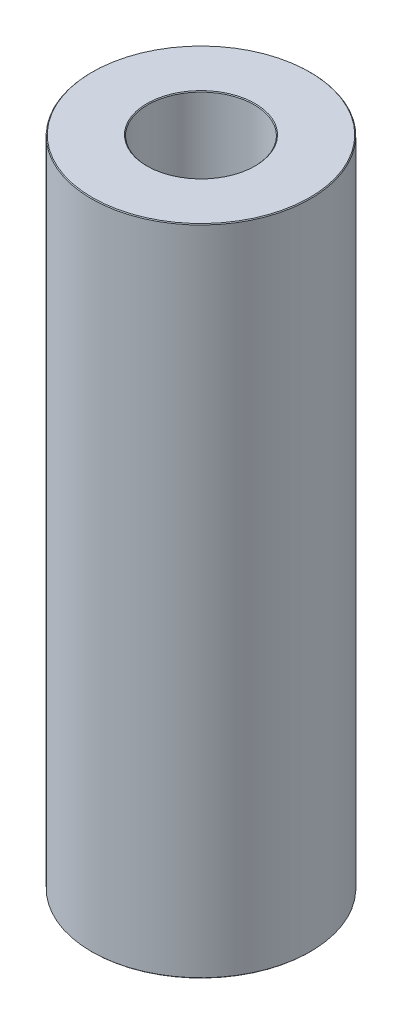
SolidWorks part; units mm, degrees
ref_plane "Front Plane" through (0, 0, 0) normal (0, 0, 1) x (1, 0, 0)
ref_plane "Top Plane" through (0, 0, 0) normal (0, 1, 0) x (1, 0, 0)
ref_plane "Right Plane" through (0, 0, 0) normal (1, 0, 0) x (0, 0, -1)
sketch "Sketch1" plane through (0, 0, 0) normal (0, 1, 0) x (1, 0, 0)
  circle A0 centre (0, 0) radius 50
  dimension "SLEEVE_OD" = 100
extrude "Boss-Extrude1" add sketch "Sketch1" along normal blind 298.4318
sketch "Sketch2" plane through (0, 0, 0) normal (0, 1, 0) x (1, 0, 0)
  circle A0 centre (0, 0) radius 24.3785
  dimension "BORE_D" = 48.7569
extrude "Cut-Extrude1" cut sketch "Sketch2" along normal through all
chamfer "Chamfer1" distance 0.3451 angle 45 4 edges at (0, 298.4318, 24.3785) (0, 0, 24.3785) (0, 0, 50) (0, 298.4318, 50)
